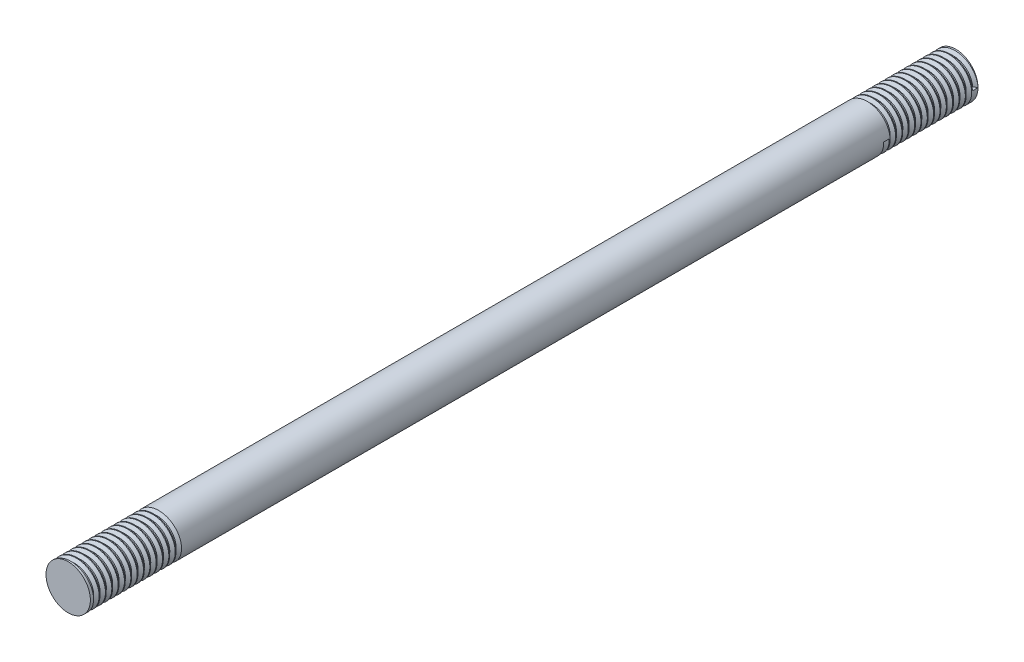
SolidWorks part; units mm, degrees
ref_plane "Front Plane" through (0, 0, 0) normal (0, 0, 1) x (1, 0, 0)
ref_plane "Top Plane" through (0, 0, 0) normal (0, 1, 0) x (1, 0, 0)
ref_plane "Right Plane" through (0, 0, 0) normal (1, 0, 0) x (0, 0, -1)
sketch "Sketch2" plane through (0, 0, 0) normal (0, 0, 1) x (1, 0, 0)
  circle A0 centre (0, 0) radius 3.175
  dimension "D1" = 6.35
extrude "Boss-Extrude1" add sketch "Sketch2" along normal blind 127
cosmetic thread "Cosmetic Thread1" parameters "D1"=5, "D2"=5.268
thread "Thread1" pitch 0.9071 method cut profile "Thread Profile1" start angle 0, offset 0, length 12.7, pitch 0.9071, diameter 6.35
ref_plane "Plane1" through (-3.175, 0, 127) normal (0, -1, 0) x (-1, 0, 0)
sketch "Thread Profile1" plane through (-3.175, 0, 127) normal (0, -1, 0) x (-1, 0, 0)
  line L0 (0, 0) -> (0, 0.9071) construction
  line L11 (0, 0) -> (0, 0.7937)
  line L12 (0, 0.7937) -> (-0.491, 0.5103)
  line L13 (-0.491, 0.5103) -> (-0.491, 0.2835)
  line L15 (-0.491, 0.2835) -> (0, 0)
  line L17 (-0.491, 0.3969) -> (0, 0.3969) construction
  point P2 (0, 0)
  dimension "Pitch" = 0.9071
  dimension "Profile_Angle" = 60
  dimension "Profile_Land" = 0.2268
  dimension "Profile_Height" = 0.491
thread "Thread2" pitch 0.9071 method cut profile "Thread Profile2" start angle 0, offset 0, length 12.7, pitch 0.9071, diameter 6.35
ref_plane "Plane2" through (3.175, 0, 0) normal (0, -1, 0) x (1, 0, 0)
sketch "Thread Profile2" plane through (3.175, 0, 0) normal (0, -1, 0) x (1, 0, 0)
  line L0 (0, 0) -> (0, 0.9071) construction
  line L11 (0, 0) -> (0, 0.7937)
  line L12 (0, 0.7937) -> (-0.491, 0.5103)
  line L13 (-0.491, 0.5103) -> (-0.491, 0.2835)
  line L15 (-0.491, 0.2835) -> (0, 0)
  line L17 (-0.491, 0.3969) -> (0, 0.3969) construction
  point P2 (0, 0)
  dimension "Pitch" = 0.9071
  dimension "Profile_Angle" = 60
  dimension "Profile_Land" = 0.2268
  dimension "Profile_Height" = 0.491
